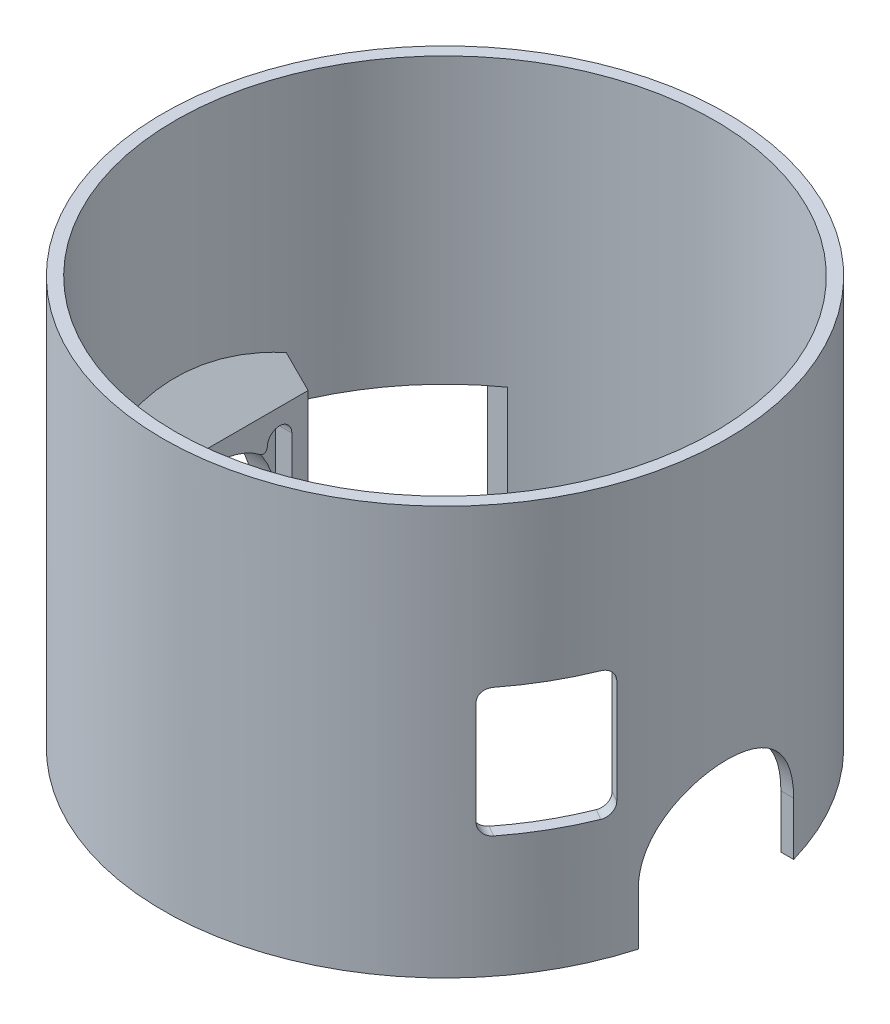
SolidWorks part; units mm, degrees
ref_plane "Front Plane" through (0, 0, 0) normal (0, 0, 1) x (1, 0, 0)
ref_plane "Top Plane" through (0, 0, 0) normal (0, 1, 0) x (1, 0, 0)
ref_plane "Right Plane" through (0, 0, 0) normal (1, 0, 0) x (0, 0, -1)
sketch "Sketch1" plane through (0, 0, 0) normal (0, 1, 0) x (1, 0, 0)
  circle A0 centre (0, 0) radius 69
  circle A1 centre (0, 0) radius 66
  dimension "D1" = 138
  dimension "D2" = 3
extrude "Boss-Extrude1" add sketch "Sketch1" along normal blind 100
sketch "Sketch2" plane through (0, 0, 0) normal (0, 1, 0) x (1, 0, 0)
  line L0 (0, 0) -> (-101.9987, 0) construction
  line L1 (0, 0) -> (-90.6575, -52.3411) construction
  line L2 (-64.9519, -37.5) -> (-82.6631, -6.8233) construction
  line L3 (0.25, -0.25) -> (126.3516, -0.25) construction
  line L4 (0.25, -0.25) -> (106.5028, -61.5951) construction
  line L5 (64.9062, -37.5792) -> (82.115, -7.7727) construction
  dimension "D1" = 30
  dimension "D2" = 75
  dimension "D3" = 30
  dimension "D4" = 75
ref_plane "Plane1" through (-64.9519, 0, 37.5) normal (0.866, 0, -0.5) x (-0.5, 0, -0.866)
sketch "Sketch3" plane through (-64.9519, 0, 37.5) normal (0.866, 0, -0.5) x (-0.5, 0, -0.866)
  line L0 (10, 31.5) -> (10, 59.5)
  line L1 (10, 59.5) -> (-10, 59.5)
  line L2 (-10, 59.5) -> (-10, 31.5)
  line L3 (-10, 31.5) -> (10, 31.5)
  point P2 (0, 31.5)
  dimension "D1" = 20
  dimension "D2" = 31.5
  dimension "D3" = 28
  dimension "D4" = 0
extrude "Cut-Extrude1" cut sketch "Sketch3" along normal up to next
fillet "Fillet1" radius 3 4 edges at (-52.8113, 31.5, 42.0376) (-62.8113, 31.5, 24.7171) (-52.8113, 59.5, 42.0376) (-62.8113, 59.5, 24.7171)
sketch "Sketch4" plane through (0, 0, 0) normal (1, 0, 0) x (0, 0, -1)
  line L1 (23.3, 0) -> (53.7, 0)
  line L2 (23.3, 0) -> (23.3, 30.4)
  line L3 (23.3, 30.4) -> (53.7, 30.4)
  line L4 (53.7, 0) -> (53.7, 30.4)
  dimension "D1" = 30.4
  dimension "D2" = 30.4
  dimension "D3" = 0
  dimension "D4" = 23.3
extrude "Cut-Extrude2" cut sketch "Sketch4" against normal through all
sketch "Sketch5" plane through (0, 0, 0) normal (1, 0, 0) x (0, 0, -1)
  line L8 (19, 13) -> (19, -6)
  line L9 (19, -6) -> (-19, -6)
  line L10 (-19, -6) -> (-19, 13)
  arc A1 (19, 13) -> (-19, 13) centre (0, 13) ccw
  dimension "D1" = 19
extrude "Cut-Extrude6" cut sketch "Sketch5" along normal through all both and the other way through all
sketch "Sketch6" plane through (0, 0, 0) normal (1, 0, 0) x (0, 0, -1)
  line L0 (19, 13) -> (19, 0)
  line L2 (-19, 0) -> (-19, 13)
  line L3 (23, 13) -> (23, 0)
  line L4 (-23, 0) -> (-23, 13)
  line L5 (23, 0) -> (19, 0)
  line L6 (-19, 0) -> (-23, 0)
  arc A0 (19, 13) -> (-19, 13) centre (0, 13) ccw
  arc A1 (23, 13) -> (-23, 13) centre (0, 13) ccw
  dimension "D1" = 19
  dimension "D3" = 0
  dimension "D2" = 4
extrude "Boss-Extrude2" add sketch "Sketch6" against normal up to next from offset 56.5 offset against normal yes
sketch "Sketch7" plane through (-56.5, 0, 0) normal (1, 0, 0) x (0, 0, -1)
  line L0 (0, 36) -> (15, 36) construction
  arc A0 (23, 13) -> (-23, 13) centre (0, 13) ccw construction
  dimension "D1" = 15
ref_plane "Plane2" through (-10.25, -10.25, 0) normal (-0.7071, -0.7071, 0) x (0, 0, -1)
sketch "Sketch8" plane through (-10.25, -10.25, 0) normal (-0.7071, -0.7071, 0) x (0, 0, -1)
  line L0 (23, -39.9515) -> (23, -49.1439) construction
  line L1 (-23, -82.9515) -> (23, -82.9515)
  line L2 (-23, -82.9515) -> (-23, -47.9515)
  line L3 (-23, -47.9515) -> (23, -47.9515)
  line L4 (23, -82.9515) -> (23, -47.9515)
  line L5 (-23, -49.1439) -> (-23, -39.9515) construction
  line L6 (19, -39.9515) -> (23, -39.9515) construction
  dimension "D1" = 0
  dimension "D2" = 0
  dimension "D3" = 8
  dimension "D4" = 35
extrude "Boss-Extrude4" add sketch "Sketch8" along normal blind 30 contours L2 L1 L4 L3
sketch "Sketch9" plane through (0, 0, 0) normal (0, -1, 0) x (1, 0, 0)
  line L12 (63.206, 19) -> (66.3325, 19)
  line L13 (-66.3325, 19) -> (-56.5, 19)
  line L14 (-56.5, 19) -> (-56.5, 23)
  line L15 (-56.5, 23) -> (-61.8628, 23)
  line L18 (-56.5, 19) -> (-56.5, 23)
  line L19 (-56.5, 23) -> (-61.8628, 23)
  line L20 (-56.5, 19) -> (-56.5, -19)
  line L24 (-56.5, -19) -> (-66.3325, -19)
  line L25 (-64.947, -23.3) -> (-61.7504, -23.3)
  line L26 (-61.8628, -23) -> (-56.5, -23)
  line L27 (-56.5, -23) -> (-56.5, -19)
  line L30 (-61.8628, -23) -> (-56.5, -23)
  line L31 (-56.5, -23) -> (-56.5, -19)
  arc A6 (66.3325, 19) -> (-66.3325, 19) centre (0, 0) ccw
  arc A7 (63.206, 19) -> (-61.8628, 23) centre (0, 0) ccw
  arc A8 (66.3325, 19) -> (-66.3325, 19) centre (0, 0) ccw
  arc A9 (63.206, 19) -> (-61.8628, 23) centre (0, 0) ccw
  arc A10 (-66.3325, -19) -> (-66.3325, 19) centre (0, 0) ccw
  arc A11 (-61.8628, -23) -> (-61.8628, 23) centre (0, 0) ccw
  arc A12 (-66.3325, -19) -> (-64.947, -23.3) centre (0, 0) ccw
  arc A13 (-61.8628, -23) -> (-61.7504, -23.3) centre (0, 0) ccw
  arc A14 (-66.3325, -19) -> (-64.947, -23.3) centre (0, 0) ccw
  arc A15 (-61.8628, -23) -> (-61.7504, -23.3) centre (0, 0) ccw
  circle A16 centre (0, 0) radius 69
  arc A18 (-61.8628, -23) -> (-61.8628, 23) centre (0, 0) ccw
  line M15 (-66.3325, 19) -> (-56.5, 19)
  line M16 (-56.5, 19) -> (-56.5, 23)
  line M17 (-56.5, 23) -> (-61.8628, 23)
  arc M18 (-61.8628, 23) -> (63.206, 19) centre (0, 0) cw
  dimension "D1" = 0
  dimension "D2" = 0
extrude "Cut-Extrude7" cut sketch "Sketch9" against normal through all flip side to cut contours A16
extrude "Cut-Extrude8" cut sketch "Sketch9<3>" against normal through all contours L31 L30 A11 M15 M18 M17 M16 region at (1.7062, 0, 0)
sketch "Sketch9<3>" plane through (0, 0, 0) normal (0, -1, 0) x (1, 0, 0) same geometry as "Sketch9"
extrude "Cut-Extrude9" cut sketch "Sketch5<2>" against normal through all
sketch "Sketch5<2>" plane through (0, 0, 0) normal (1, 0, 0) x (0, 0, -1) same geometry as "Sketch5"
ref_plane "Plane3" through (64.9519, 0, 37.5) normal (0.866, 0, 0.5) x (0.5, 0, -0.866)
sketch "Sketch10" plane through (64.9519, 0, 37.5) normal (0.866, 0, 0.5) x (0.5, 0, -0.866)
  line L0 (-11.6, 61.25) -> (11.6, 61.25) construction
  line L1 (-12.6, 61.25) -> (12.6, 61.25)
  line L2 (-12.6, 61.25) -> (-12.6, 29.75)
  line L3 (-12.6, 29.75) -> (12.6, 29.75)
  line L4 (12.6, 61.25) -> (12.6, 29.75)
  line L5 (12.6, 60.25) -> (12.6, 30.75) construction
  line L6 (11.6, 29.75) -> (-11.6, 29.75) construction
  line L7 (-12.6, 30.75) -> (-12.6, 60.25) construction
  dimension "D1" = 0
  dimension "D2" = 0
  dimension "D3" = 0
  dimension "D4" = 0
extrude "Cut-Extrude10" cut sketch "Sketch10" against normal up to next contours L2 L3 L4 L1
fillet "Fillet2" radius 3 4 edges at (51.1287, 29.75, 44.0684) (51.1287, 61.25, 44.0684) (63.7287, 61.25, 22.2446) (63.7287, 29.75, 22.2446)
sketch "Sketch11" plane through (-56.5, 0, 0) normal (1, 0, 0) x (0, 0, -1)
  line L0 (-19, 29) -> (-19, 11)
  line L1 (-19, 0) -> (-19, 13) construction
  line L2 (-19, 11) -> (-13, 11)
  line L3 (-13, 11) -> (-13, 29)
  line L4 (13, 29) -> (13, 11)
  line L5 (19, 29) -> (19, 11)
  line L6 (19, 13) -> (19, 0) construction
  line L7 (13, 11) -> (19, 11)
  arc A0 (19, 29) -> (13, 29) centre (16, 29) ccw
  arc A1 (-13, 29) -> (-19, 29) centre (-16, 29) ccw
  dimension "D1" = 6
  dimension "D2" = 6
  dimension "D3" = 18
  dimension "D4" = 18
extrude "Cut-Extrude11" cut sketch "Sketch11" against normal blind 4
fillet "Fillet3" radius 1 2 edges at (-58.5, 26.8564, -13) (-58.5, 26.8564, 13)
